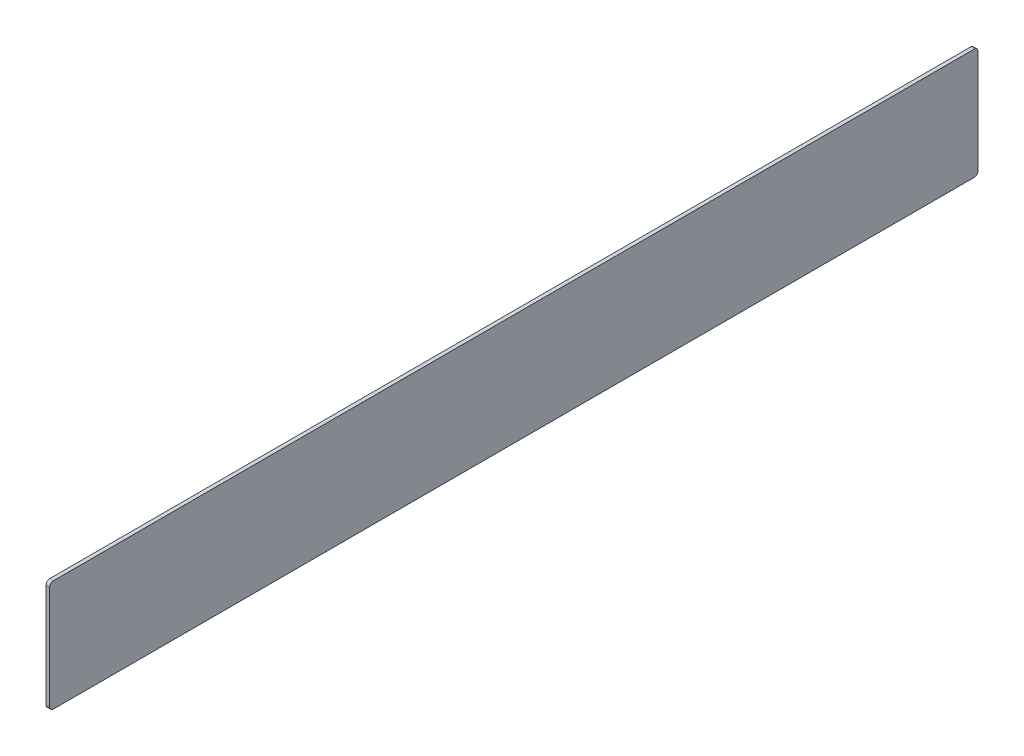
SolidWorks part; units mm, degrees
ref_plane "Front Plane" through (0, 0, 0) normal (0, 0, 1) x (1, 0, 0)
ref_plane "Top Plane" through (0, 0, 0) normal (0, 1, 0) x (1, 0, 0)
ref_plane "Right Plane" through (0, 0, 0) normal (1, 0, 0) x (0, 0, -1)
sketch "Sketch1" plane through (0, 0, 0) normal (1, 0, 0) x (0, 0, -1)
  line L1 (-269.9468, -80.4426) -> (230.0532, -80.4426)
  line L2 (-269.9468, -80.4426) -> (-269.9468, -140.2926)
  line L3 (-269.9468, -140.2926) -> (230.0532, -140.2926)
  line L4 (230.0532, -80.4426) -> (230.0532, -140.2926)
  dimension "D1" = 500
  dimension "D2" = 59.85
extrude "Boss-Extrude1" add sketch "Sketch1" along normal blind 2
fillet "Fillet1" radius 2 4 edges at (1, -140.2926, -230.0532) (1, -80.4426, -230.0532) (1, -140.2926, 269.9468) (1, -80.4426, 269.9468)
